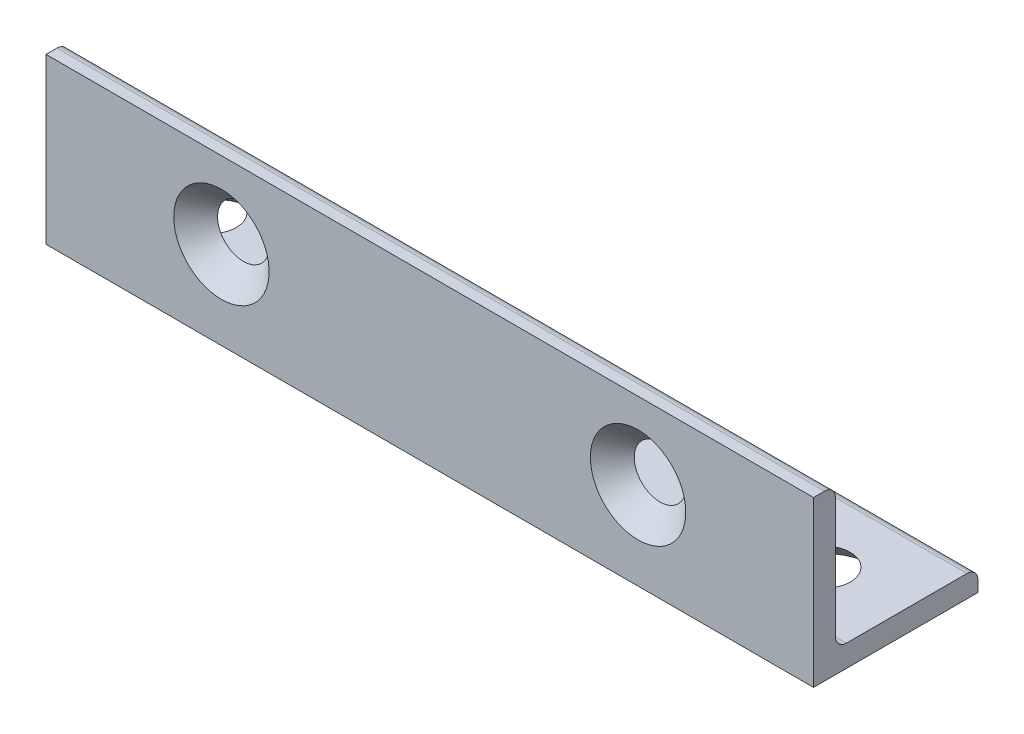
SolidWorks part; units mm, degrees
material "1060 Сплав"
ref_plane "Front" through (0, 0, 0) normal (0, 0, 1) x (1, 0, 0)
ref_plane "Top" through (0, 0, 0) normal (0, 1, 0) x (1, 0, 0)
ref_plane "Right" through (0, 0, 0) normal (1, 0, 0) x (0, 0, -1)
sketch "Эскиз1" plane through (0, 0, 0) normal (1, 0, 0) x (0, 0, -1)
  line L0 (0, 0) -> (0, 15)
  line L1 (0, 0) -> (15, 0)
  line L2 (0, 15) -> (1, 15)
  line L3 (2, 14) -> (2, 3)
  line L4 (3, 2) -> (14, 2)
  line L5 (15, 1) -> (15, 0)
  arc A0 (14, 2) -> (15, 1) centre (14, 1) cw
  arc A1 (1, 15) -> (2, 14) centre (1, 14) cw
  arc A2 (2, 3) -> (3, 2) centre (3, 3) ccw
  point P9 (15, 2)
  point P12 (2, 15)
  dimension "D5" = 1
  dimension "D1" = 15
  dimension "D2" = 15
  dimension "D3" = 2
  dimension "D4" = 2
extrude "Бобышка-Вытянуть1" add sketch "Эскиз1" along normal blind 70
sketch "Эскиз2" plane through (0, 2, 0) normal (0, 1, 0) x (1, 0, 0)
  line L0 (0, 14) -> (0, 3) construction
  line L1 (70, 15) -> (0, 15) construction
  circle A0 centre (7, 8) radius 2.3
  circle A1 centre (63, 8) radius 2.3
  dimension "D1" = 4.6
  dimension "D2" = 4.6
  dimension "D3" = 56
  dimension "D4" = 7
  dimension "D5" = 7
  dimension "D6" = 7
extrude "Вырез-Вытянуть1" cut sketch "Эскиз2" against normal through all
sketch "Эскиз3" plane through (0, 0, -2) normal (0, 0, -1) x (-1, 0, 0)
  line L0 (-70, 15) -> (0, 15) construction
  line L1 (0, 3) -> (0, 14) construction
  circle A0 centre (-16, 8) radius 2.3
  circle A1 centre (-54, 8) radius 2.3
  dimension "D1" = 4.6
  dimension "D2" = 4.6
  dimension "D3" = 7
  dimension "D4" = 7
  dimension "D5" = 38
  dimension "D6" = 16
extrude "Вырез-Вытянуть2" cut sketch "Эскиз3" against normal through all
chamfer "Фаска1" distance 2.05 angle 45 4 edges at (63, 0, -5.7) (7, 0, -5.7) (54, 10.3, 0) (16, 10.3, 0)
